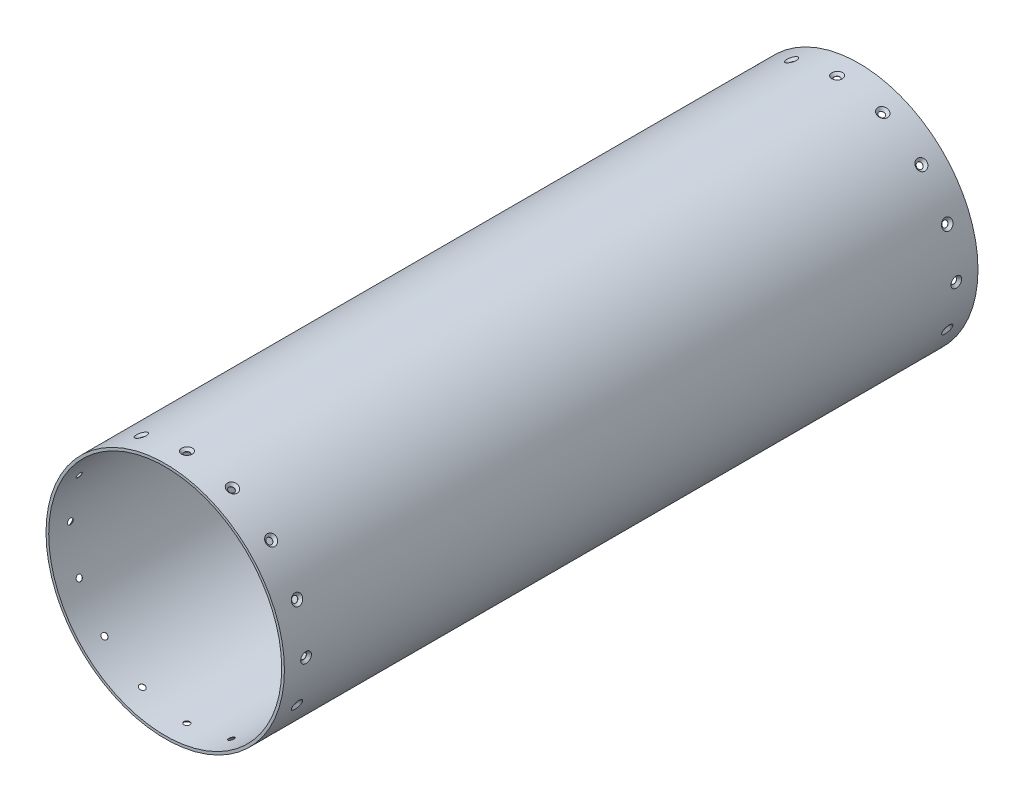
SolidWorks part; units mm, degrees
material "6061-T6 (SS)"
ref_plane "Front Plane" through (0, 0, 0) normal (0, 0, 1) x (1, 0, 0)
ref_plane "Top Plane" through (0, 0, 0) normal (0, 1, 0) x (1, 0, 0)
ref_plane "Right Plane" through (0, 0, 0) normal (1, 0, 0) x (0, 0, -1)
sketch "Sketch1" plane through (0, 0, 0) normal (0, 0, 1) x (1, 0, 0)
  circle A0 centre (0, 0) radius 69.85
  circle A1 centre (0, 0) radius 68.2625
  dimension "D1" = 139.7
  dimension "D2" = 1.5875
extrude "Extrude1" add sketch "Sketch1" along normal blind 406.4
ref_plane "Plane1" through (0, 0, 12.7) normal (0, 0, -1) x (-1, 0, 0)
sketch "Sketch2" plane through (0, 0, 12.7) normal (0, 0, -1) x (-1, 0, 0)
  line L0 (0, 0) -> (0, -69.85) construction
  line L1 (0, 0) -> (-13.6271, -68.5079) construction
  circle A0 centre (0, 0) radius 69.85 construction
  circle A1 centre (0, 0) radius 69.85 construction
  dimension "D1" = 11.25
ref_plane "Plane2" through (0, -69.85, 12.7) normal (0, -1, 0) x (1, 0, 0)
hole_wizard "CSK for M3 Flat Head Machine Screw1" positions "Sketch5" profile "Sketch4" countersink size "M3" standard "Ansi Metric" end condition through all
sketch "Sketch5" plane through (0, -69.85, 12.7) normal (0, -1, 0) x (1, 0, 0)
  point P2 (0, 0)
sketch "Sketch4" plane through (0, -69.85, 12.7) normal (1, 0, 0) x (0, 0, -1)
  line L0 (0, 0) -> (0, 161.1134)
  line L1 (0, 161.1134) -> (1.7, 161.1134)
  line L2 (1.7, 161.1134) -> (1.7, 1.45)
  line L3 (1.7, 1.45) -> (3.15, 0)
  line L5 (3.15, 0) -> (0, 0)
  line L6 (-1.7, 1.45) -> (-3.15, 0) construction
  line L11 (0, -6.35) -> (0, 107.95) construction
  dimension "Thru Hole Dia." = 3.4
  dimension "Thru Hole Depth" = 161.1134
  dimension "Near C'Sink Dia." = 6.3
  dimension "Near C'Sink Angle" = 90
pattern_circular "CirPattern1" count 16 over 360 about axis through (0, 0, 406.4) along (0, 0, -1) of "CSK for M3 Flat Head Machine Screw1"
ref_plane "Plane3" through (0, 0, 395.2875) normal (0, 0, 1) x (1, 0, 0)
ref_plane "Plane5" through (0, 0, 0) normal (0.8315, 0.5556, 0) x (-0.5556, 0.8315, 0)
ref_plane "Plane7" through (0, 0, 0) normal (0.5556, -0.8315, 0) x (0.8315, 0.5556, 0)
ref_plane "Plane9" through (0, 0, 0) normal (-0.1951, -0.9808, 0) x (0.9808, -0.1951, 0)
sketch "Sketch7" plane through (0, 0, 406.4) normal (0, 0, 1) x (1, 0, 0)
  circle A0 centre (0, 0) radius 69.85 construction
  point P0 (69.85, 0)
ref_plane "Plane8" through (-68.5079, 13.6271, 203.2) normal (-0.9808, 0.1951, 0) x (0.1951, 0.9808, 0)
sketch "Sketch8" plane through (-68.5079, 13.6271, 203.2) normal (-0.9808, 0.1951, 0) x (0.1951, 0.9808, 0)
  line L0 (0, -425.45) -> (0, -414.3248) construction
pattern_linear "LPattern1" count 2 spacing 381 along (0, 0, 1) of "CirPattern1"
ref_plane "Plane10" through (13.6271, -68.5079, 12.7) normal (0.1951, -0.9808, 0) x (0.9808, 0.1951, 0)
hole_wizard "#10 Clearance Hole4" positions "Sketch13" profile "Sketch12" hole size "#10" standard "Ansi Inch"
sketch "Sketch13" plane through (13.6271, -68.5079, 12.7) normal (0.1951, -0.9808, 0) x (0.9808, 0.1951, 0)
  point P3 (0, 0)
sketch "Sketch12" plane through (13.6271, -68.5079, 12.7) normal (0, 0, 1) x (0.9808, 0.1951, 0)
  line L0 (0, 0) -> (0, 14.2338)
  line L1 (0, 14.2338) -> (2.5527, 12.7)
  line L2 (2.5527, 12.7) -> (2.5527, 0)
  line L5 (2.5527, 0) -> (0, 0)
  line L10 (0, 14.2338) -> (-2.5527, 12.7) construction
  line L11 (0, -6.35) -> (0, 107.95) construction
  dimension "Hole Dia." = 5.1054
  dimension "Hole Depth" = 12.7
  dimension "Drill Angle" = 118
sketch3d "3DSketch2"
  spline S0 degree 3 poles (-49.2458, -49.537, 9.55) (-49.537, -49.2458, 9.55) (-49.6797, -49.1019, 9.5709) (-49.9593, -48.8173, 9.653) (-50.0975, -48.6754, 9.7152) (-50.3575, -48.4064, 9.8758) (-50.4805, -48.278, 9.974) (-50.7128, -48.034, 10.2067) (-50.8205, -47.9199, 10.3402) (-51.0138, -47.7141, 10.6321) (-51.1009, -47.6207, 10.7927) (-51.2525, -47.4576, 11.1372) (-51.3157, -47.3891, 11.3178) (-51.4182, -47.2778, 11.6952) (-51.4577, -47.2348, 11.894) (-51.5096, -47.1782, 12.2943) (-51.5226, -47.164, 12.4963) (-51.5226, -47.164, 12.9042) (-51.5092, -47.1787, 13.1104) (-51.4571, -47.2355, 13.5091) (-51.4185, -47.2776, 13.7041) (-51.2632, -47.4461, 14.2749) (-51.1116, -47.6099, 14.6206) (-50.8185, -47.922, 15.0627) (-50.7121, -48.0347, 15.1939) (-50.4818, -48.2767, 15.4248) (-50.3563, -48.4077, 15.5252) (-50.0958, -48.6772, 15.6856) (-49.9607, -48.8158, 15.7465) (-49.6807, -49.1008, 15.8289) (-49.5356, -49.2472, 15.8499) (-49.1047, -49.6781, 15.8501) (-48.8121, -49.9654, 15.7657) (-48.4092, -50.3548, 15.5262) (-48.2783, -50.4803, 15.4261) (-48.0349, -50.7119, 15.1942) (-47.9223, -50.8183, 15.0629) (-47.7153, -51.0127, 14.7699) (-47.6211, -51.1006, 14.6078) (-47.4592, -51.2509, 14.2666) (-47.3904, -51.3145, 14.0861) (-47.2777, -51.4183, 13.7048) (-47.2354, -51.4572, 13.5087) (-47.1786, -51.5092, 13.1101) (-47.164, -51.5226, 12.9051) (-47.164, -51.5226, 12.4958) (-47.1783, -51.5096, 12.2937) (-47.2348, -51.4577, 11.8944) (-47.2778, -51.4183, 11.6954) (-47.3892, -51.3156, 11.3174) (-47.4576, -51.2524, 11.1372) (-47.6198, -51.1018, 10.7945) (-47.7139, -51.0139, 10.6323) (-47.9197, -50.8207, 10.3404) (-48.0321, -50.7145, 10.2087) (-48.2767, -50.4818, 9.9751) (-48.4061, -50.3578, 9.876) (-48.6742, -50.0987, 9.7159) (-48.8147, -49.9618, 9.6539) (-49.1013, -49.6802, 9.5709) (-49.2458, -49.537, 9.55) (-49.537, -49.2458, 9.55) (-49.6797, -49.1019, 9.5709) knots -0.03125 -0.03125 0 0 0.03125 0.03125 0.0625 0.0625 0.09375 0.09375 0.125 0.125 0.15625 0.15625 0.1875 0.1875 0.21875 0.21875 0.25 0.25 0.28125 0.28125 0.3125 0.3125 0.375 0.375 0.40625 0.40625 0.4375 0.4375 0.46875 0.46875 0.5 0.5 0.5625 0.5625 0.59375 0.59375 0.625 0.625 0.65625 0.65625 0.6875 0.6875 0.71875 0.71875 0.75 0.75 0.78125 0.78125 0.8125 0.8125 0.84375 0.84375 0.875 0.875 0.90625 0.90625 0.9375 0.9375 0.96875 0.96875 1 1 1.03125 1.03125 1.0625 only from (-49.3914, -49.3914, 9.55) to (-49.3914, -49.3914, 9.55) construction
  spline S1 degree 3 poles (-49.2458, -49.537, 9.55) (-49.537, -49.2458, 9.55) (-49.6797, -49.1019, 9.5709) (-49.9593, -48.8173, 9.653) (-50.0975, -48.6754, 9.7152) (-50.3575, -48.4064, 9.8758) (-50.4805, -48.278, 9.974) (-50.7128, -48.034, 10.2067) (-50.8205, -47.9199, 10.3402) (-51.0138, -47.7141, 10.6321) (-51.1009, -47.6207, 10.7927) (-51.2525, -47.4576, 11.1372) (-51.3157, -47.3891, 11.3178) (-51.4182, -47.2778, 11.6952) (-51.4577, -47.2348, 11.894) (-51.5096, -47.1782, 12.2943) (-51.5226, -47.164, 12.4963) (-51.5226, -47.164, 12.9042) (-51.5092, -47.1787, 13.1104) (-51.4571, -47.2355, 13.5091) (-51.4185, -47.2776, 13.7041) (-51.2632, -47.4461, 14.2749) (-51.1116, -47.6099, 14.6206) (-50.8185, -47.922, 15.0627) (-50.7121, -48.0347, 15.1939) (-50.4818, -48.2767, 15.4248) (-50.3563, -48.4077, 15.5252) (-50.0958, -48.6772, 15.6856) (-49.9607, -48.8158, 15.7465) (-49.6807, -49.1008, 15.8289) (-49.5356, -49.2472, 15.8499) (-49.1047, -49.6781, 15.8501) (-48.8121, -49.9654, 15.7657) (-48.4092, -50.3548, 15.5262) (-48.2783, -50.4803, 15.4261) (-48.0349, -50.7119, 15.1942) (-47.9223, -50.8183, 15.0629) (-47.7153, -51.0127, 14.7699) (-47.6211, -51.1006, 14.6078) (-47.4592, -51.2509, 14.2666) (-47.3904, -51.3145, 14.0861) (-47.2777, -51.4183, 13.7048) (-47.2354, -51.4572, 13.5087) (-47.1786, -51.5092, 13.1101) (-47.164, -51.5226, 12.9051) (-47.164, -51.5226, 12.4958) (-47.1783, -51.5096, 12.2937) (-47.2348, -51.4577, 11.8944) (-47.2778, -51.4183, 11.6954) (-47.3892, -51.3156, 11.3174) (-47.4576, -51.2524, 11.1372) (-47.6198, -51.1018, 10.7945) (-47.7139, -51.0139, 10.6323) (-47.9197, -50.8207, 10.3404) (-48.0321, -50.7145, 10.2087) (-48.2767, -50.4818, 9.9751) (-48.4061, -50.3578, 9.876) (-48.6742, -50.0987, 9.7159) (-48.8147, -49.9618, 9.6539) (-49.1013, -49.6802, 9.5709) (-49.2458, -49.537, 9.55) (-49.537, -49.2458, 9.55) (-49.6797, -49.1019, 9.5709) knots -0.03125 -0.03125 0 0 0.03125 0.03125 0.0625 0.0625 0.09375 0.09375 0.125 0.125 0.15625 0.15625 0.1875 0.1875 0.21875 0.21875 0.25 0.25 0.28125 0.28125 0.3125 0.3125 0.375 0.375 0.40625 0.40625 0.4375 0.4375 0.46875 0.46875 0.5 0.5 0.5625 0.5625 0.59375 0.59375 0.625 0.625 0.65625 0.65625 0.6875 0.6875 0.71875 0.71875 0.75 0.75 0.78125 0.78125 0.8125 0.8125 0.84375 0.84375 0.875 0.875 0.90625 0.90625 0.9375 0.9375 0.96875 0.96875 1 1 1.03125 1.03125 1.0625 only from (-49.3914, -49.3914, 9.55) to (-49.3914, -49.3914, 9.55)
  spline S2 degree 3 poles (48.068, -50.6805, 10.1702) (47.8425, -50.8934, 10.441) (47.7408, -50.9888, 10.5897) (47.5587, -51.1586, 10.9125) (47.4781, -51.2334, 11.0883) (47.3446, -51.3567, 11.4526) (47.291, -51.4061, 11.6421) (47.2102, -51.4803, 12.0361) (47.1837, -51.5045, 12.2392) (47.1476, -51.5376, 12.8462) (47.1814, -51.5068, 13.2617) (47.314, -51.385, 13.8432) (47.3724, -51.3311, 14.0336) (47.5143, -51.1998, 14.3939) (47.597, -51.1231, 14.5626) (47.7851, -50.9473, 14.8773) (47.8919, -50.847, 15.0243) (48.1202, -50.631, 15.2829) (48.2422, -50.5148, 15.3958) (48.5022, -50.2652, 15.5882) (48.6397, -50.1322, 15.6667) (48.9182, -49.8605, 15.7824) (49.0609, -49.7202, 15.8208) (49.3519, -49.4314, 15.8565) (49.4955, -49.2875, 15.8532) (49.7795, -49.0007, 15.8062) (49.9212, -48.8562, 15.7616) (50.1914, -48.5786, 15.6337) (50.3202, -48.4451, 15.551) (50.5655, -48.189, 15.3485) (50.6816, -48.0669, 15.2284) (50.9968, -47.733, 14.8276) (51.1705, -47.5461, 14.4963) (51.3556, -47.3459, 13.9513) (51.406, -47.2911, 13.7584) (51.4801, -47.2104, 13.365) (51.5041, -47.1842, 13.1652) (51.5266, -47.1597, 12.7592) (51.5246, -47.1618, 12.5519) (51.4947, -47.1945, 12.1477) (51.467, -47.2247, 11.9489) (51.3854, -47.3135, 11.558) (51.3315, -47.372, 11.3678) (51.2014, -47.5126, 11.0101) (51.1247, -47.5952, 10.8405) (50.9469, -47.7855, 10.5219) (50.8486, -47.8902, 10.3779) (50.6334, -48.1176, 10.1197) (50.5151, -48.2419, 10.0045) (50.2655, -48.5019, 9.812) (50.135, -48.6368, 9.7347) (49.8626, -48.916, 9.6182) (49.7196, -49.0614, 9.5792) (49.4343, -49.3489, 9.5438) (49.2905, -49.4925, 9.5464) (49.001, -49.7792, 9.5936) (48.8579, -49.9196, 9.6379) (48.5814, -50.1887, 9.7648) (48.446, -50.3194, 9.8483) (48.1888, -50.5658, 10.0516) (48.068, -50.6805, 10.1702) (47.8425, -50.8934, 10.441) (47.7408, -50.9888, 10.5897) knots -0.03125 -0.03125 0 0 0.03125 0.03125 0.0625 0.0625 0.09375 0.09375 0.125 0.125 0.1875 0.1875 0.21875 0.21875 0.25 0.25 0.28125 0.28125 0.3125 0.3125 0.34375 0.34375 0.375 0.375 0.40625 0.40625 0.4375 0.4375 0.46875 0.46875 0.5 0.5 0.5625 0.5625 0.59375 0.59375 0.625 0.625 0.65625 0.65625 0.6875 0.6875 0.71875 0.71875 0.75 0.75 0.78125 0.78125 0.8125 0.8125 0.84375 0.84375 0.875 0.875 0.90625 0.90625 0.9375 0.9375 0.96875 0.96875 1 1 1.03125 1.03125 1.0625 only from (47.9552, -50.787, 10.3056) to (47.9552, -50.787, 10.3056) construction
  spline S3 degree 3 poles (48.068, -50.6805, 10.1702) (47.8425, -50.8934, 10.441) (47.7408, -50.9888, 10.5897) (47.5587, -51.1586, 10.9125) (47.4781, -51.2334, 11.0883) (47.3446, -51.3567, 11.4526) (47.291, -51.4061, 11.6421) (47.2102, -51.4803, 12.0361) (47.1837, -51.5045, 12.2392) (47.1476, -51.5376, 12.8462) (47.1814, -51.5068, 13.2617) (47.314, -51.385, 13.8432) (47.3724, -51.3311, 14.0336) (47.5143, -51.1998, 14.3939) (47.597, -51.1231, 14.5626) (47.7851, -50.9473, 14.8773) (47.8919, -50.847, 15.0243) (48.1202, -50.631, 15.2829) (48.2422, -50.5148, 15.3958) (48.5022, -50.2652, 15.5882) (48.6397, -50.1322, 15.6667) (48.9182, -49.8605, 15.7824) (49.0609, -49.7202, 15.8208) (49.3519, -49.4314, 15.8565) (49.4955, -49.2875, 15.8532) (49.7795, -49.0007, 15.8062) (49.9212, -48.8562, 15.7616) (50.1914, -48.5786, 15.6337) (50.3202, -48.4451, 15.551) (50.5655, -48.189, 15.3485) (50.6816, -48.0669, 15.2284) (50.9968, -47.733, 14.8276) (51.1705, -47.5461, 14.4963) (51.3556, -47.3459, 13.9513) (51.406, -47.2911, 13.7584) (51.4801, -47.2104, 13.365) (51.5041, -47.1842, 13.1652) (51.5266, -47.1597, 12.7592) (51.5246, -47.1618, 12.5519) (51.4947, -47.1945, 12.1477) (51.467, -47.2247, 11.9489) (51.3854, -47.3135, 11.558) (51.3315, -47.372, 11.3678) (51.2014, -47.5126, 11.0101) (51.1247, -47.5952, 10.8405) (50.9469, -47.7855, 10.5219) (50.8486, -47.8902, 10.3779) (50.6334, -48.1176, 10.1197) (50.5151, -48.2419, 10.0045) (50.2655, -48.5019, 9.812) (50.135, -48.6368, 9.7347) (49.8626, -48.916, 9.6182) (49.7196, -49.0614, 9.5792) (49.4343, -49.3489, 9.5438) (49.2905, -49.4925, 9.5464) (49.001, -49.7792, 9.5936) (48.8579, -49.9196, 9.6379) (48.5814, -50.1887, 9.7648) (48.446, -50.3194, 9.8483) (48.1888, -50.5658, 10.0516) (48.068, -50.6805, 10.1702) (47.8425, -50.8934, 10.441) (47.7408, -50.9888, 10.5897) knots -0.03125 -0.03125 0 0 0.03125 0.03125 0.0625 0.0625 0.09375 0.09375 0.125 0.125 0.1875 0.1875 0.21875 0.21875 0.25 0.25 0.28125 0.28125 0.3125 0.3125 0.34375 0.34375 0.375 0.375 0.40625 0.40625 0.4375 0.4375 0.46875 0.46875 0.5 0.5 0.5625 0.5625 0.59375 0.59375 0.625 0.625 0.65625 0.65625 0.6875 0.6875 0.71875 0.71875 0.75 0.75 0.78125 0.78125 0.8125 0.8125 0.84375 0.84375 0.875 0.875 0.90625 0.90625 0.9375 0.9375 0.96875 0.96875 1 1 1.03125 1.03125 1.0625 only from (47.9552, -50.787, 10.3056) to (47.9552, -50.787, 10.3056)
